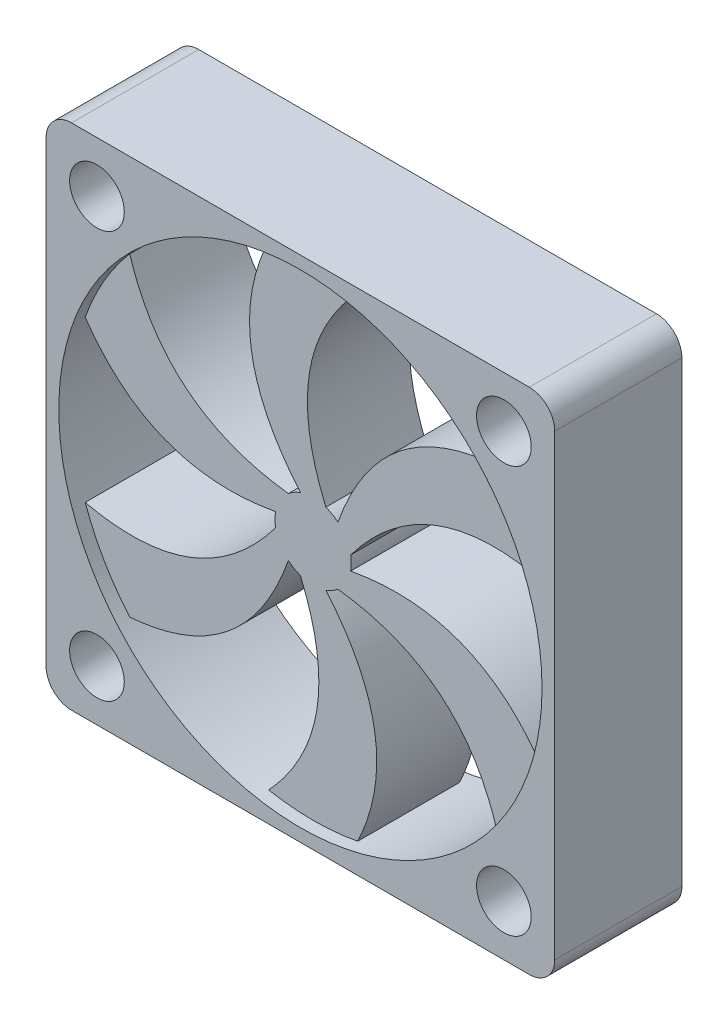
SolidWorks part; units mm, degrees
ref_plane "Front Plane" through (0, 0, 0) normal (0, 0, 1) x (1, 0, 0)
ref_plane "Top Plane" through (0, 0, 0) normal (0, 1, 0) x (1, 0, 0)
ref_plane "Right Plane" through (0, 0, 0) normal (1, 0, 0) x (0, 0, -1)
sketch "Sketch1" plane through (0, 0, 0) normal (0, 0, 1) x (1, 0, 0)
  line L0 (-5, 12.6748) -> (0, 12.6748) construction
  line L1 (-18, -20) -> (18, -20)
  line L2 (-20, -18) -> (-20, 18)
  line L3 (-18, 20) -> (18, 20)
  line L4 (20, -18) -> (20, 18)
  line L5 (-20, -20) -> (20, 20) construction
  line L6 (-20, 20) -> (20, -20) construction
  line L7 (0, 18.6748) -> (0, 12.6748)
  line L8 (-3.5, 18.6748) -> (3.5, 18.6748) construction
  line L9 (-1, 2.8284) -> (1, 2.8284) construction
  line L10 (8.4767, 10.6676) -> (10.9767, 6.3374) construction
  line L11 (14.4229, 12.3685) -> (17.9229, 6.3063) construction
  line L12 (1.9495, 2.2802) -> (2.9495, 0.5482) construction
  line L13 (13.4767, -2.0073) -> (10.9767, -6.3374) construction
  line L14 (17.9229, -6.3063) -> (14.4229, -12.3685) construction
  line L15 (2.9495, -0.5482) -> (1.9495, -2.2802) construction
  line L16 (5, -12.6748) -> (0, -12.6748) construction
  line L17 (3.5, -18.6748) -> (-3.5, -18.6748) construction
  line L18 (1, -2.8284) -> (-1, -2.8284) construction
  line L19 (-8.4767, -10.6676) -> (-10.9767, -6.3374) construction
  line L20 (-14.4229, -12.3685) -> (-17.9229, -6.3063) construction
  line L21 (-1.9495, -2.2802) -> (-2.9495, -0.5482) construction
  line L22 (-13.4767, 2.0073) -> (-10.9767, 6.3374) construction
  line L23 (-17.9229, 6.3063) -> (-14.4229, 12.3685) construction
  line L24 (-2.9495, 0.5482) -> (-1.9495, 2.2802) construction
  circle A0 centre (-16, 16) radius 2.15
  circle A1 centre (16, 16) radius 2.15
  circle A2 centre (16, -16) radius 2.15
  circle A3 centre (-16, -16) radius 2.15
  circle A4 centre (0, 0) radius 19
  circle A5 centre (0, 0) radius 3
  arc A6 (-18, -20) -> (-20, -18) centre (-18, -18) cw
  arc A7 (18, -20) -> (20, -18) centre (18, -18) ccw
  arc A8 (20, 18) -> (18, 20) centre (18, 18) ccw
  arc A9 (-20, 18) -> (-18, 20) centre (-18, 18) cw
  spline S0 degree 2 poles (1, 2.8284) (-2.8443, 11.8557) (3.5, 18.6748) knots 0 0 0 1 1 1
  spline S1 degree 2 poles (-1, 2.8284) (-7.4527, 10.3845) (-3.5, 18.6748) knots 0 0 0 1 1 1
  spline S2 degree 2 poles (1.9495, 2.2802) (5.2669, 11.6465) (14.4229, 12.3685) knots 0 0 0 1 1 1
  spline S3 degree 2 poles (2.9495, 0.5482) (8.8452, 8.3911) (17.9229, 6.3063) knots 0 0 0 1 1 1
  spline S4 degree 2 poles (2.9495, -0.5482) (12.7196, 1.2619) (17.9229, -6.3063) knots 0 0 0 1 1 1
  spline S5 degree 2 poles (1.9495, -2.2802) (11.6896, -3.4646) (14.4229, -12.3685) knots 0 0 0 1 1 1
  spline S6 degree 2 poles (1, -2.8284) (7.4527, -10.3845) (3.5, -18.6748) knots 0 0 0 1 1 1
  spline S7 degree 2 poles (-1, -2.8284) (2.8443, -11.8557) (-3.5, -18.6748) knots 0 0 0 1 1 1
  spline S8 degree 2 poles (-1.9495, -2.2802) (-5.2669, -11.6465) (-14.4229, -12.3685) knots 0 0 0 1 1 1
  spline S9 degree 2 poles (-2.9495, -0.5482) (-8.8452, -8.3911) (-17.9229, -6.3063) knots 0 0 0 1 1 1
  spline S10 degree 2 poles (-2.9495, 0.5482) (-12.7196, -1.2619) (-17.9229, 6.3063) knots 0 0 0 1 1 1
  spline S11 degree 2 poles (-1.9495, 2.2802) (-11.6896, 3.4646) (-14.4229, 12.3685) knots 0 0 0 1 1 1
  point P0 (0, 0)
  point P33 (0, 2.8284)
  point P34 (0, 18.6748)
  point P39 (-18.4524, 2.5239)
  point P40 (-10.9767, 6.3374)
  point P82 (0, 0)
  point P83 (-13.4767, 2.0073)
  point P84 (-18, 6.3374)
  point P85 (5, -12.6748)
  dimension "D2" = 4.3
  dimension "D3" = 32
  dimension "D4" = 38
  dimension "D5" = 6
  dimension "D6" = 2
  dimension "D1" = 40
  dimension "D7" = 6
  dimension "D8" = 5
  dimension "D9" = 2
  dimension "D10" = 7
  dimension "D11" = 6
extrude "Boss-Extrude1" add sketch "Sketch1" along normal mid plane 10 contours A9 L2 A6 L1 A7 L4 A8 L3 A4 A3 A2 A1 A0 region at (-19.0142, -19.0142, 0)
extrude "Boss-Extrude2" add sketch "Sketch1<5>" along normal mid plane 8 contours A5 S11 A4 S10 | S1 A5 S0 A4 | A5 S3 A4 S2 | A5 S5 A4 S4 | A5 S7 A4 S6 | A5 S9 A4 S8 | A5 region at (9.7638, 7.6375, 0) region at (11.4962, -4.6369, 0) region at (0, 0, 0) region at (-1.7324, 12.2745, 0) region at (1.7324, -12.2745, 0) region at (-11.4962, 4.6369, 0) region at (-9.7638, -7.6375, 0)
sketch "Sketch1<5>" plane through (0, 0, 0) normal (0, 0, 1) x (1, 0, 0) same geometry as "Sketch1"
